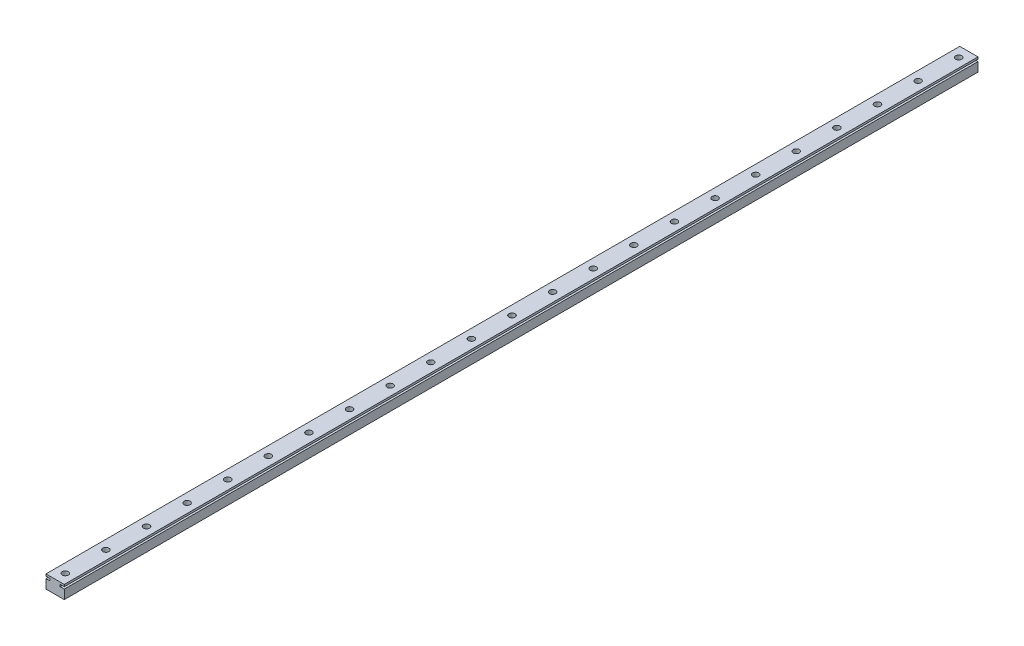
SolidWorks part; units mm, degrees
ref_plane "前视基准面" through (0, 0, 0) normal (0, 0, 1) x (1, 0, 0)
ref_plane "上视基准面" through (0, 0, 0) normal (0, 1, 0) x (1, 0, 0)
ref_plane "右视基准面" through (0, 0, 0) normal (1, 0, 0) x (0, 0, -1)
other "Configuration Table"
sketch "草图1" plane through (0, 0, 0) normal (0, 0, 1) x (1, 0, 0)
  line L1 (0, 0) -> (-9, 0)
  line L2 (0, 0) -> (0, 6.5)
  line L3 (0, 6.5) -> (-9, 6.5)
  line L4 (-9, 0) -> (-9, 6.5)
  dimension "D1" = 9
  dimension "D2" = 6.5
extrude "凸台-拉伸1" add sketch "草图1" along normal blind 450
sketch "草图2" plane through (0, 0, 0) normal (0, 0, -1) x (-1, 0, 0)
  line L0 (0, 6.5) -> (0, 5.5) construction
  line L1 (0, 0) -> (0, 6.5) construction
  line L2 (2, 5.5) -> (0, 5.5)
  line L3 (2, 4.5) -> (0, 4.5)
  line L4 (0, 4.5) -> (0, 5.5)
  line L5 (2, 5.5) -> (2, 4.5)
  line L6 (4.5, 6.5) -> (4.5, 5.0177) construction
  line L7 (0, 6.5) -> (9, 6.5) construction
  line L8 (7, 5.5) -> (9, 5.5)
  line L9 (9, 4.5) -> (9, 5.5)
  line L10 (7, 4.5) -> (9, 4.5)
  line L11 (7, 5.5) -> (7, 4.5)
  dimension "D1" = 1
  dimension "D2" = 1
  dimension "D3" = 2
extrude "切除-拉伸1" cut sketch "草图2" against normal blind 450
sketch "草图3" plane through (0, 6.5, 0) normal (0, 1, 0) x (1, 0, 0)
  line L0 (-4.5, 0) -> (-4.5, -5) construction
  line L1 (0, 0) -> (-9, 0) construction
  circle A0 centre (-4.5, -5) radius 1.5
  circle A1 centre (-4.5, -25) radius 1.5
  circle A2 centre (-4.5, -45) radius 1.5
  circle A3 centre (-4.5, -65) radius 1.5
  circle A4 centre (-4.5, -85) radius 1.5
  circle A5 centre (-4.5, -105) radius 1.5
  circle A6 centre (-4.5, -125) radius 1.5
  circle A7 centre (-4.5, -145) radius 1.5
  circle A8 centre (-4.5, -165) radius 1.5
  circle A9 centre (-4.5, -185) radius 1.5
  circle A10 centre (-4.5, -205) radius 1.5
  circle A11 centre (-4.5, -225) radius 1.5
  circle A12 centre (-4.5, -245) radius 1.5
  circle A13 centre (-4.5, -265) radius 1.5
  circle A14 centre (-4.5, -285) radius 1.5
  circle A15 centre (-4.5, -305) radius 1.5
  circle A16 centre (-4.5, -325) radius 1.5
  circle A17 centre (-4.5, -345) radius 1.5
  circle A18 centre (-4.5, -365) radius 1.5
  circle A19 centre (-4.5, -385) radius 1.5
  circle A20 centre (-4.5, -405) radius 1.5
  circle A21 centre (-4.5, -425) radius 1.5
  circle A22 centre (-4.5, -445) radius 1.5
  dimension "D2" = 3
  dimension "D1" = 5
  dimension "D3" = 23
extrude "切除-拉伸2" cut sketch "草图3" against normal up to next
